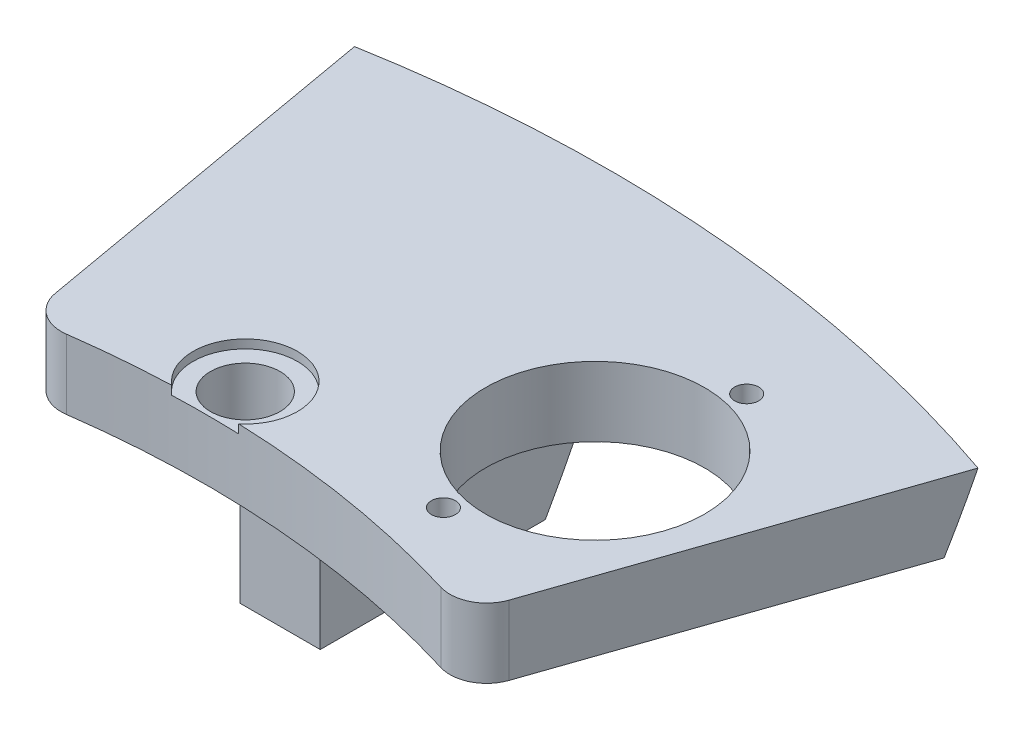
SolidWorks part; units mm, degrees
material "PUR"
ref_plane "Front Plane" through (0, 0, 0) normal (0, 0, 1) x (1, 0, 0)
ref_plane "Top Plane" through (0, 0, 0) normal (0, 1, 0) x (1, 0, 0)
ref_plane "Right Plane" through (0, 0, 0) normal (1, 0, 0) x (0, 0, -1)
sketch "Sketch1" plane through (0, 0, 0) normal (1, 0, 0) x (0, 0, -1)
  line L0 (130.175, 13.6878) -> (181.9184, 13.6878) construction
  line L4 (0, -200000) -> (0, 218797.9879) construction
  line L5 (130.175, 13.6878) -> (181.9184, 13.6878)
  line L6 (130.175, 13.6878) -> (130.175, 23.2128)
  line L7 (130.175, 23.2128) -> (185.5699, 23.2128)
  line L9 (135.5719, -24.4122) -> (135.5719, 13.6878) construction
  line L10 (135.5719, 13.6878) -> (135.5719, 23.2128) construction
  line L11 (0, -24.4122) -> (142.875, -24.4122) construction
  arc A0 (0, -107.9583) -> (166.6461, 193.6724) centre (0, 88.8917) ccw construction
  arc A3 (181.9184, 13.6878) -> (185.5699, 23.2128) centre (0, 88.8917) ccw
revolve "Revolve1" add sketch "Sketch1" angle 20 mid plane about L4
sketch "Sketch2" plane through (0, 23.2128, 0) normal (0, 1, 0) x (1, 0, 0)
  line L0 (0, 0) -> (38.5822, 181.5148) construction
  line L1 (42.3808, 123.0829) -> (60.4157, 175.4598)
  line L3 (-32.2239, 182.7507) -> (-22.6047, 128.1973)
  line L4 (22.6047, 128.1973) -> (32.2239, 182.7507)
  line L5 (-32.2239, 182.7507) -> (-22.6047, 128.1973)
  line L6 (22.6047, 128.1973) -> (32.2239, 182.7507)
  circle A0 centre (28.5203, 134.1774) radius 2
  circle A1 centre (35.7972, 168.4126) radius 2
  arc A2 (32.2239, 182.7507) -> (-32.2239, 182.7507) centre (0, 0) ccw construction
  arc A5 (22.6047, 128.1973) -> (-22.6047, 128.1973) centre (0, 0) ccw
  arc A6 (32.2239, 182.7507) -> (-32.2239, 182.7507) centre (0, 0) ccw
  arc A7 (42.3808, 123.0829) -> (-22.6047, 128.1973) centre (0, 0) ccw
  arc A8 (60.4157, 175.4598) -> (-32.2239, 182.7507) centre (0, 0) ccw
  line M9 (22.6047, 128.1973) -> (32.2239, 182.7507)
  dimension "D2" = 4
  dimension "D1" = 35
  dimension "D4" = 7
  dimension "D5" = 7
  dimension "D6" = 2
  dimension "D3" = 0
extrude "Boss-Extrude1" add sketch "Sketch2" against normal up to surface (9.525 mm away) contours L0 A7 L1 A8 A1 A0 | A7 L0 A0 A1 A8 M9 | L0 A0 | A0 L0 | L0 A1 | A1 L0 region at (30.3925, 23.2128, -156.7722) region at (42.7103, 23.2128, -153.6255) region at (27.69, 23.2128, -134.3539) region at (29.3506, 23.2128, -134.0009) region at (34.9669, 23.2128, -168.589) region at (36.6275, 23.2128, -168.2361) up to face at (0, 13.6878, -154.8613)
other "DeleteFace1" face at (32.0161, 16.8549, -181.5723) face at (46.3914, 18.4503, -179.3822) and patch yes
sketch "Sketch3" plane through (0, 23.2128, 0) normal (0, 1, 0) x (1, 0, 0)
  circle A0 centre (0, 135.5719) radius 7.1438
  dimension "D1" = 14.2875
extrude "Cut-Extrude1" cut sketch "Sketch3" against normal blind 1.1906
sketch "Sketch4" plane through (0, 22.0222, 0) normal (0, 1, 0) x (1, 0, 0)
  circle A0 centre (0, 135.5719) radius 4.7625
  dimension "D1" = 9.525
extrude "Cut-Extrude2" cut sketch "Sketch4" against normal through all
sketch "Sketch5" plane through (0, 13.6878, 0) normal (0, -1, 0) x (1, 0, 0)
  line L1 (32.1587, -151.295) -> (46.831, -148.1763) construction
  line L2 (0, 0) -> (38.5822, -181.5148) construction
  circle A0 centre (32.1587, -151.295) radius 15
  circle A1 centre (28.5203, -134.1774) radius 2 construction
  circle A2 centre (35.7972, -168.4126) radius 2 construction
  dimension "D1" = 30
extrude "Cut-Extrude3" cut sketch "Sketch5" against normal through all
fillet "Fillet1" radius 2 rebuild error yes
fillet "Fillet2" radius 5 2 edges at (-22.6047, 18.4503, -128.1973) (42.3808, 18.4503, -123.0829)
sketch "Sketch6" plane through (0, 13.6878, 0) normal (0, -1, 0) x (1, 0, 0)
  line L0 (0, -140.3344) -> (0, -181.9184) construction
  line L1 (-5.5, -140.3344) -> (-5.5, -181.9184)
  line L2 (-5.5, -140.3344) -> (5.5, -140.3344)
  line L3 (5.5, -140.3344) -> (5.5, -181.9184)
  line L4 (-5.5, -181.9184) -> (5.5, -181.9184)
  circle A2 centre (0, -135.5719) radius 4.7625 construction
  arc A3 (-31.5898, -179.1546) -> (59.2268, -172.0072) centre (0, 0) ccw construction
  point P11 (0, -135.5719)
  dimension "D1" = 11
extrude "Boss-Extrude2" add sketch "Sketch6" along normal blind 21.89
other "DeleteFace2" face at (0, 4.9318, -181.9184) face at (-3.6668, 13.6878, -181.8976) and patch yes
sketch "Sketch7" plane through (0, -8.2022, 0) normal (0, -1, 0) x (1, 0, 0)
  line L0 (-5.5, -140.3344) -> (-5.5, -181.8352) construction
  line L1 (21.6687, -141.0719) -> (31.6687, -141.0719)
  line L2 (21.6687, -141.0719) -> (21.6687, 122.8895)
  line L3 (21.6687, 122.8895) -> (31.6687, 179.6023)
  line L4 (31.6687, -141.0719) -> (31.6687, 179.6023)
  line L5 (-23.4568, -133.0303) -> (-31.5898, -179.1546) construction
  line L6 (-5.5, -140.3344) -> (-5.5, -171.1504) construction
  point P11 (26.6687, -141.0719)
  dimension "D1" = 10
hole_wizard "M4x0.7 Tapped Hole1" positions "Sketch8" profile "Sketch9" tap size "M4x0.7" standard "ANSI Metric" end condition through all
sketch "Sketch8" plane through (0, 23.2128, 0) normal (0, 1, 0) x (1, 0, 0)
  point P0 (35.7972, 168.4126)
  point P3 (28.5203, 134.1774)
sketch "Sketch9" plane through (35.7972, 23.2128, -168.4126) normal (1, 0, 0) x (0, 0, 1)
  line L0 (0, 0) -> (0, 31.415)
  line L1 (0, 31.415) -> (1.65, 31.415)
  line L2 (1.65, 31.415) -> (1.65, 0)
  line L5 (1.65, 0) -> (0, 0)
  line L11 (0, -6.35) -> (0, 107.95) construction
  dimension "Thru Tap Drill Dia." = 3.3
  dimension "Thru Tap Drill Depth" = 31.415
cosmetic thread "Hole Thread1" parameters "D2"=4
cosmetic thread "Hole Thread2" parameters "D2"=4
